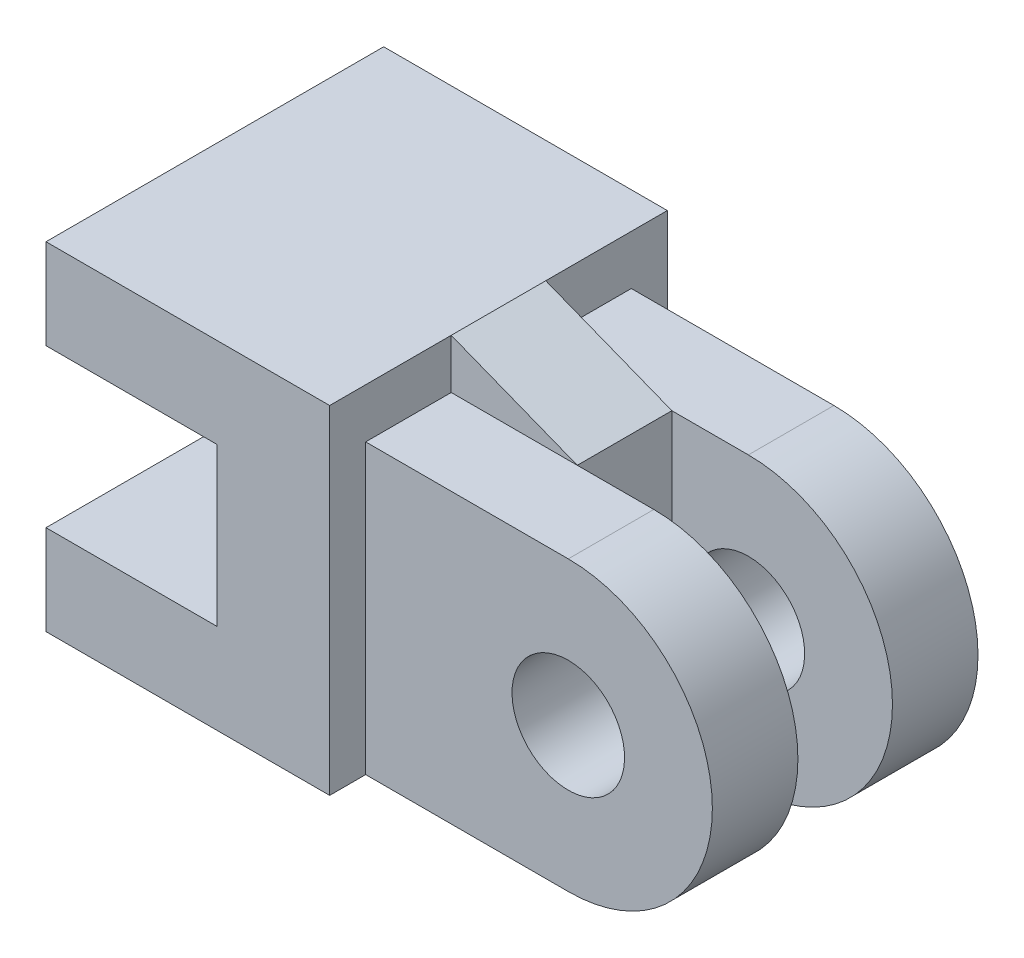
SolidWorks part; units mm, degrees
ref_plane "Ön Düzlem" through (0, 0, 0) normal (0, 0, 1) x (1, 0, 0)
ref_plane "Üst Düzlem" through (0, 0, 0) normal (0, 1, 0) x (1, 0, 0)
ref_plane "Sağ Düzlem" through (0, 0, 0) normal (1, 0, 0) x (0, 0, -1)
sketch "Çizim1" plane through (0, 0, 0) normal (0, 0, 1) x (1, 0, 0)
  line L0 (-87.5762, -10.1682) -> (-87.5762, -30.1682)
  line L1 (-87.5762, 44.8318) -> (-24.5762, 44.8318)
  line L2 (-87.5762, 44.8318) -> (-87.5762, 24.8318)
  line L3 (-87.5762, -30.1682) -> (-24.5762, -30.1682)
  line L4 (-24.5762, 44.8318) -> (-24.5762, -30.1682)
  line L5 (-87.5762, 24.8318) -> (-49.5762, 24.8318)
  line L7 (-87.5762, -10.1682) -> (-49.5762, -10.1682)
  line L8 (-49.5762, 24.8318) -> (-49.5762, -10.1682)
  dimension "D1" = 63
  dimension "D2" = 35
  dimension "D3" = 38
  dimension "D4" = 20
  dimension "D5" = 20
extrude "Yükseklik-Ekstrüzyon1" add sketch "Çizim1" along normal blind 75
sketch "Çizim3" plane through (-24.5762, 0, 0) normal (1, 0, 0) x (0, 0, -1)
  line L0 (-75, -30.1682) -> (0, -30.1682) construction
  line L1 (-67, 33.8318) -> (-48, 33.8318)
  line L2 (-67, 33.8318) -> (-67, -30.1682)
  line L3 (-67, -30.1682) -> (-48, -30.1682)
  line L4 (-48, 33.8318) -> (-48, -30.1682)
  line L5 (-75, 44.8318) -> (0, 44.8318) construction
  line L6 (-27, 33.8318) -> (-8, 33.8318)
  line L7 (-27, 33.8318) -> (-27, -30.1682)
  line L8 (-27, -30.1682) -> (-8, -30.1682)
  line L9 (-8, 33.8318) -> (-8, -30.1682)
  line L10 (-75, -30.1682) -> (-75, 44.8318) construction
  line L11 (0, -30.1682) -> (0, 44.8318) construction
  dimension "D1" = 11
  dimension "D2" = 11
  dimension "D3" = 8
  dimension "D4" = 8
  dimension "D5" = 19
  dimension "D6" = 19
extrude "Yükseklik-Ekstrüzyon6" add sketch "Çizim3" along normal blind 77 contours L2 L1 L4 L3 | L7 L6 L9 L8
fillet "Radyus1" 2 edges at (52.4238, 33.8318, 57.5) (52.4238, -30.1682, 57.5) type full round first side face at (13.9238, 33.8318, 57.5) second side face at (-9.4095, -30.1682, 37.5) middle face at (52.4238, 1.8318, 57.5)
fillet "Radyus2" 2 edges at (52.4238, 33.8318, 17.5) (52.4238, -30.1682, 17.5) type full round first side face at (13.9238, 33.8318, 17.5) second side face at (-14.7429, -30.1682, 37.5) middle face at (52.4238, 1.8318, 17.5)
sketch "Çizim4" plane through (0, 0, 67) normal (0, 0, 1) x (1, 0, 0)
  line L0 (-24.5762, 33.8318) -> (-24.5762, -30.1682) construction
  line L1 (20.4238, 33.8318) -> (-24.5762, 33.8318) construction
  circle A0 centre (20.4238, 1.8318) radius 12.5
  point P4 (0, 0)
  dimension "D1" = 25
  dimension "D2" = 45
  dimension "D3" = 32
extrude "Kes-Ekstrüzyon1" cut sketch "Çizim4" against normal through all both and the other way through all
sketch "Çizim6" plane through (-24.5762, 0, 0) normal (1, 0, 0) x (0, 0, -1)
  line L0 (-75, 44.8318) -> (0, 44.8318) construction
  line L1 (-48, 44.8318) -> (-27, 44.8318)
  line L2 (-48, 44.8318) -> (-48, -30.1682)
  line L3 (-48, -30.1682) -> (-27, -30.1682)
  line L4 (-27, 44.8318) -> (-27, -30.1682)
extrude "Yükseklik-Ekstrüzyon7" add sketch "Çizim6" along normal blind 28
sketch "Çizim7" plane through (0, 0, 48) normal (0, 0, 1) x (1, 0, 0)
  line L0 (-24.5762, 44.8318) -> (3.4238, 33.8318)
  line L1 (3.4238, 33.8318) -> (3.4238, 44.8318)
  line L2 (3.4238, 44.8318) -> (-24.5762, 44.8318)
extrude "Kes-Ekstrüzyon3" cut sketch "Çizim7" against normal up to next
